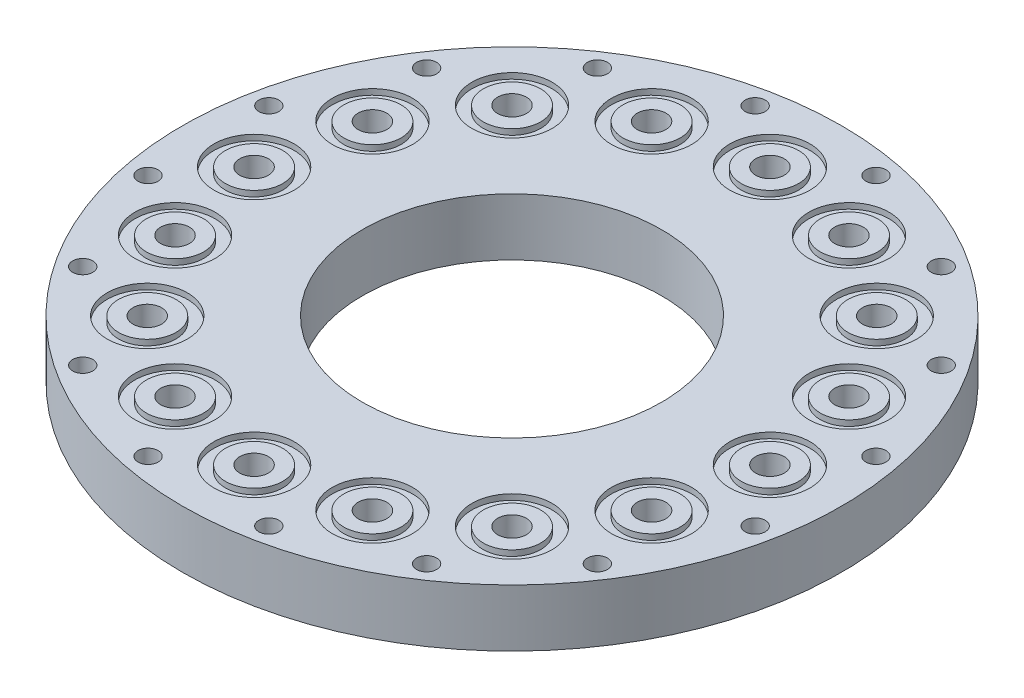
SolidWorks part; units mm, degrees
ref_plane "Front Plane" through (0, 0, 0) normal (0, 0, 1) x (1, 0, 0)
ref_plane "Top Plane" through (0, 0, 0) normal (0, 1, 0) x (1, 0, 0)
ref_plane "Right Plane" through (0, 0, 0) normal (1, 0, 0) x (0, 0, -1)
sketch "Sketch1" plane through (0, 0, 0) normal (0, 1, 0) x (1, 0, 0)
  line L0 (-10.5349, 52.9624) -> (0, 0) construction
  line L1 (0, 0) -> (62.7639, 0) construction
  line L2 (-17.2208, 41.5746) -> (0, 0) construction
  line L3 (0, 0) -> (0, 45) construction
  circle A0 centre (0, 0) radius 57.5
  circle A1 centre (0, 0) radius 54 construction
  circle A2 centre (-10.5349, 52.9624) radius 1.75
  circle A3 centre (10.5349, 52.9624) radius 1.75
  circle A4 centre (30.0008, 44.8994) radius 1.75
  circle A5 centre (44.8994, 30.0008) radius 1.75
  circle A6 centre (52.9624, 10.5349) radius 1.75
  circle A7 centre (52.9624, -10.5349) radius 1.75
  circle A8 centre (44.8994, -30.0008) radius 1.75
  circle A9 centre (30.0008, -44.8994) radius 1.75
  circle A10 centre (10.5349, -52.9624) radius 1.75
  circle A11 centre (-10.5349, -52.9624) radius 1.75
  circle A12 centre (-30.0008, -44.8994) radius 1.75
  circle A13 centre (-44.8994, -30.0008) radius 1.75
  circle A14 centre (0, 0) radius 26.1
  circle A15 centre (0, 0) radius 45 construction
  circle A16 centre (0, 45) radius 2.5
  circle A17 centre (17.2208, 41.5746) radius 2.5
  circle A18 centre (31.8198, 31.8198) radius 2.5
  circle A19 centre (41.5746, 17.2208) radius 2.5
  circle A20 centre (45, 0) radius 2.5
  circle A21 centre (41.5746, -17.2208) radius 2.5
  circle A22 centre (31.8198, -31.8198) radius 2.5
  circle A23 centre (17.2208, -41.5746) radius 2.5
  circle A24 centre (0, -45) radius 2.5
  circle A25 centre (-17.2208, -41.5746) radius 2.5
  circle A26 centre (-31.8198, -31.8198) radius 2.5
  circle A27 centre (-41.5746, -17.2208) radius 2.5
  circle A28 centre (-45, 0) radius 2.5
  circle A29 centre (-41.5746, 17.2208) radius 2.5
  circle A30 centre (-31.8198, 31.8198) radius 2.5
  circle A31 centre (-17.2208, 41.5746) radius 2.5
  circle A32 centre (-52.9624, -10.5349) radius 1.75
  circle A33 centre (-52.9624, 10.5349) radius 1.75
  circle A34 centre (-44.8994, 30.0008) radius 1.75
  circle A35 centre (-30.0008, 44.8994) radius 1.75
  point P31 (0, 0)
  point P55 (0, 0)
  dimension "D1" = 115
  dimension "D2" = 108
  dimension "D3" = 3.5
  dimension "D4" = 52.2
  dimension "D5" = 90
  dimension "D6" = 5
  dimension "D9" = 11.25
  dimension "D10" = 11.25
  dimension "D8" = 16
  dimension "D7" = 16
extrude "Boss-Extrude1" add sketch "Sketch1" along normal blind 10
sketch "Sketch2" plane through (0, 10, 0) normal (0, 1, 0) x (1, 0, 0)
  circle A0 centre (0, 0) radius 45 construction
  circle A1 centre (0, 45) radius 7
  circle A2 centre (17.2208, 41.5746) radius 7
  circle A3 centre (31.8198, 31.8198) radius 7
  circle A4 centre (41.5746, 17.2208) radius 7
  circle A5 centre (45, 0) radius 7
  circle A6 centre (41.5746, -17.2208) radius 7
  circle A7 centre (31.8198, -31.8198) radius 7
  circle A8 centre (17.2208, -41.5746) radius 7
  circle A9 centre (0, -45) radius 7
  circle A10 centre (-17.2208, -41.5746) radius 7
  circle A11 centre (-31.8198, -31.8198) radius 7
  circle A12 centre (0, 45) radius 5
  circle A13 centre (17.2208, 41.5746) radius 5
  circle A14 centre (31.8198, 31.8198) radius 5
  circle A15 centre (41.5746, 17.2208) radius 5
  circle A16 centre (45, 0) radius 5
  circle A17 centre (41.5746, -17.2208) radius 5
  circle A18 centre (31.8198, -31.8198) radius 5
  circle A19 centre (17.2208, -41.5746) radius 5
  circle A20 centre (0, -45) radius 5
  circle A21 centre (-17.2208, -41.5746) radius 5
  circle A22 centre (-31.8198, -31.8198) radius 5
  circle A23 centre (-41.5746, -17.2208) radius 5
  circle A24 centre (-45, 0) radius 5
  circle A25 centre (-41.5746, 17.2208) radius 5
  circle A26 centre (-31.8198, 31.8198) radius 5
  circle A27 centre (-17.2208, 41.5746) radius 5
  circle A28 centre (-41.5746, -17.2208) radius 7
  circle A29 centre (-45, 0) radius 7
  circle A30 centre (-41.5746, 17.2208) radius 7
  circle A31 centre (-31.8198, 31.8198) radius 7
  circle A32 centre (-17.2208, 41.5746) radius 7
  point P28 (0, 0)
  point P51 (0, 0)
  dimension "D1" = 14
  dimension "D3" = 10
  dimension "D2" = 16
  dimension "D4" = 16
extrude "Cut-Extrude1" cut sketch "Sketch2" against normal blind 1
